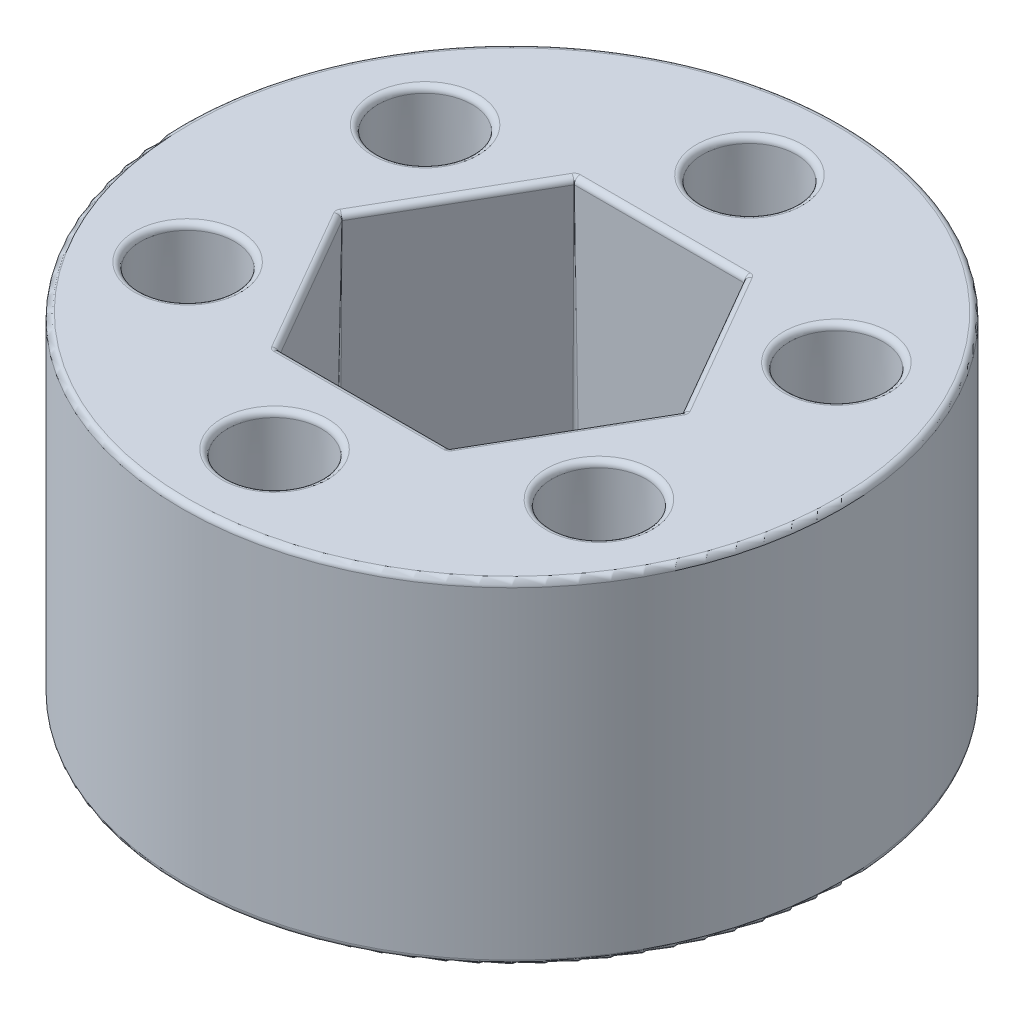
SolidWorks part; units mm, degrees
material "PP Film"
ref_plane "Front Plane" through (0, 0, 0) normal (0, 0, 1) x (1, 0, 0)
ref_plane "Top Plane" through (0, 0, 0) normal (0, 1, 0) x (1, 0, 0)
ref_plane "Right Plane" through (0, 0, 0) normal (1, 0, 0) x (0, 0, -1)
sketch "Sketch1" plane through (0, 0, 0) normal (0, 1, 0) x (1, 0, 0)
  line L7 (3.8275, -6.6294) -> (7.655, 0)
  line L8 (7.655, 0) -> (3.8275, 6.6294)
  line L9 (3.8275, 6.6294) -> (-3.8275, 6.6294)
  line L10 (-3.8275, 6.6294) -> (-7.655, 0)
  line L11 (-7.655, 0) -> (-3.8275, -6.6294)
  line L12 (-3.8275, -6.6294) -> (3.8275, -6.6294)
  circle A0 centre (0, 0) radius 14.2748
  circle A1 centre (0, 0) radius 6.6294 construction
  dimension "D1" = 28.5496
  dimension "D2" = 13.2588
extrude "Boss-Extrude1" add sketch "Sketch1" along normal blind 14.478
fillet "Fillet1" radius 0.254 6 edges at (3.8275, 7.239, -6.6294) (7.655, 7.239, 0) (3.8275, 7.239, 6.6294) (-3.8275, 7.239, 6.6294) (-7.655, 7.239, 0) (-3.8275, 7.239, -6.6294)
sketch "Sketch2" plane through (0, 14.478, 0) normal (0, 1, 0) x (1, 0, 0)
  line L0 (0, 0) -> (0, 10.287) construction
  circle A0 centre (0, 10.287) radius 2.286
  dimension "D1" = 4.572
  dimension "D2" = 10.287
extrude "Cut-Extrude1" cut sketch "Sketch2" against normal through all
pattern_circular "CirPattern1" count 6 over 360 about axis through (0, 14.478, 0) along (0, -1, 0) of "Cut-Extrude1"
draft "Draft1" type of draft neutral plane draft angle 1 faces to draft 18 face at (-7.5987, 7.239, 0) face at (-3.7993, 7.239, -6.5806) face at (-5.7412, 7.239, -3.3147) face at (0, 7.239, -6.6294) face at (3.7993, 7.239, -6.5806) face at (7.5987, 7.239, 0) face at (5.7412, 7.239, -3.3147) face at (5.7412, 7.239, 3.3147) face at (3.7993, 7.239, 6.5806) face at (-5.7412, 7.239, 3.3147) face at (-3.7993, 7.239, 6.5806) face at (0, 0, -8.001) face at (6.9291, 0, -4.0005) face at (6.9291, 0, 4.0005) face at (0, 7.239, 6.6294) face at (0, 0, 8.001) face at (-6.9291, 0, 4.0005) face at (-6.9291, 0, -4.0005) neutral plane through (0, 0, 0) neutral plane normal (0, -1, 0) parameters "D1"=1
fillet "Fillet2" radius 0.254 38 edges at (-7.363, 14.478, 0) (-5.5224, 14.478, -3.1883) (-3.6815, 14.478, -6.3765) (0, 14.478, -6.3767) (3.6815, 14.478, -6.3765) (5.5224, 14.478, -3.1883) (7.363, 14.478, 0) (5.5224, 14.478, 3.1883) (3.6815, 14.478, 6.3765) (0, 14.478, 6.3767) (-3.6815, 14.478, 6.3765) (-5.5224, 14.478, 3.1883) (0, 14.478, 14.2748) (-3.8078, 0, -6.5954) (0, 0, -6.6294) (3.8078, 0, -6.5954) (5.7412, 0, -3.3147) (7.6157, 0, 0) (5.7412, 0, 3.3147) (3.8078, 0, 6.5954) (0, 0, 6.6294) (-3.8078, 0, 6.5954) (-5.7412, 0, 3.3147) (-7.6157, 0, 0) (-5.7412, 0, -3.3147) (-6.9291, 0, -4.0005) (0, 0, 14.2748) (0, 0, -8.001) (6.9291, 0, -4.0005) (6.9291, 0, 4.0005) (0, 0, 8.001) (-6.9291, 0, 4.0005) (0, 14.478, -8.2537) (8.9088, 14.478, -3.1102) (8.9088, 14.478, 7.1768) (0, 14.478, 12.3203) (-8.9088, 14.478, 7.1768) (-8.9088, 14.478, -3.1102)
